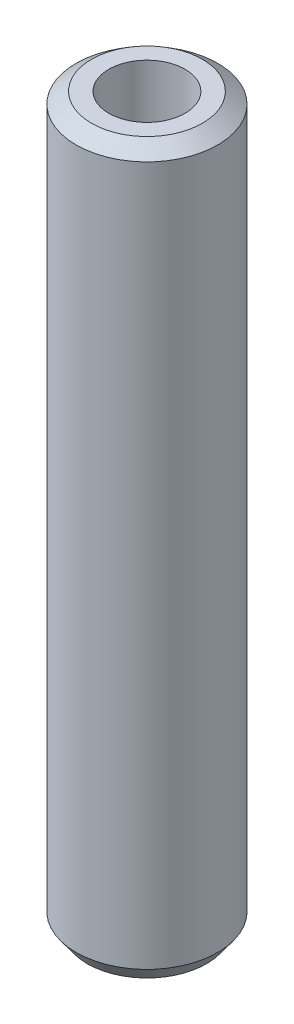
SolidWorks part; units mm, degrees
ref_plane "Front Plane" through (0, 0, 0) normal (0, 0, 1) x (1, 0, 0)
ref_plane "Top Plane" through (0, 0, 0) normal (0, 1, 0) x (1, 0, 0)
ref_plane "Right Plane" through (0, 0, 0) normal (1, 0, 0) x (0, 0, -1)
sketch "Sketch1" plane through (0, 0, 0) normal (0, 1, 0) x (1, 0, 0)
  circle A0 centre (0, 0) radius 15
  dimension "SHAFT_OD" = 30
extrude "Boss-Extrude1" add sketch "Sketch1" along normal blind 153.7756
sketch "Sketch2" plane through (0, 0, 0) normal (0, 1, 0) x (1, 0, 0)
  circle A0 centre (0, 0) radius 8.0838
  dimension "BORE_D" = 16.1677
extrude "Cut-Extrude1" cut sketch "Sketch2" along normal through all
chamfer "Chamfer1" distance 2.3566 angle 54.053 2 edges at (0, 153.7756, 15) (0, 0, 15) first distance on face at (0, 153.7756, 15) first distance on face at (0, 0, 8.0838)
